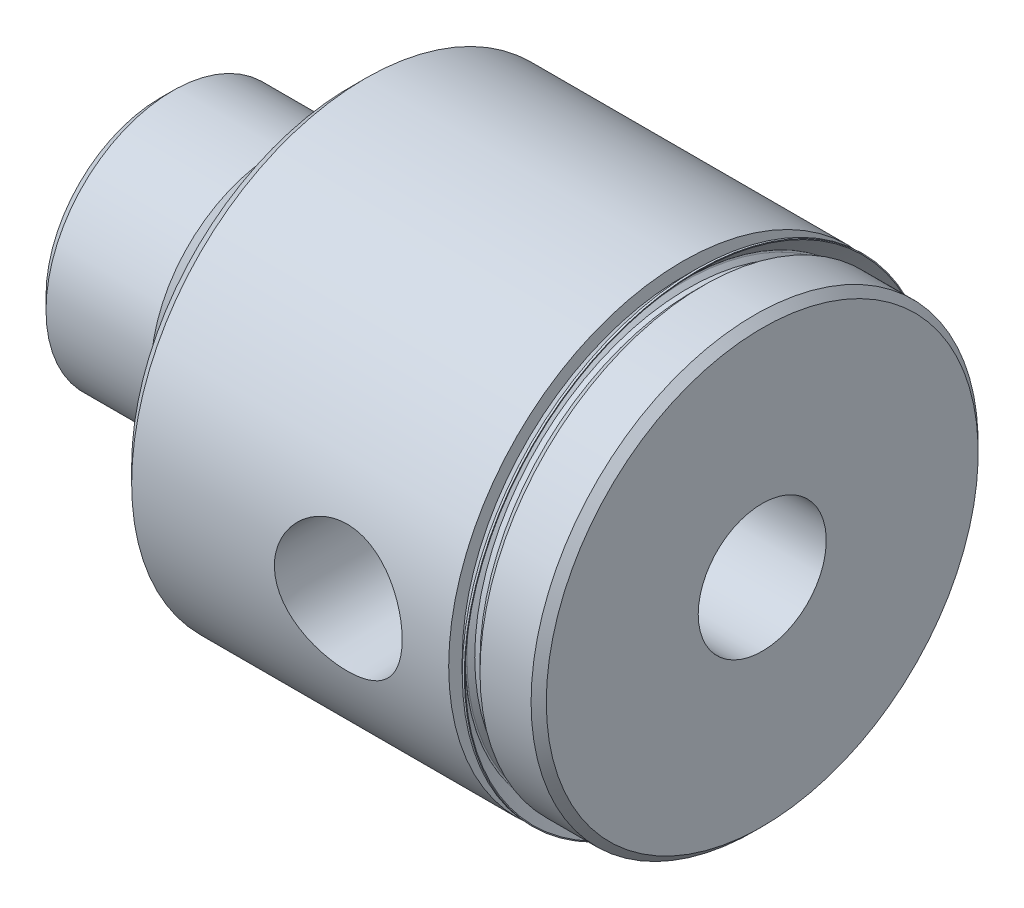
SolidWorks part; units mm, degrees
material "Cast Alloy Steel"
ref_plane "Front Plane" through (0, 0, 0) normal (0, 0, 1) x (1, 0, 0)
ref_plane "Top Plane" through (0, 0, 0) normal (0, 1, 0) x (1, 0, 0)
ref_plane "Right Plane" through (0, 0, 0) normal (1, 0, 0) x (0, 0, -1)
sketch "Sketch1" plane through (0, 0, 0) normal (0, 0, 1) x (1, 0, 0)
  line L0 (0, 0) -> (0, 11.4313)
  line L1 (0, 11.4313) -> (1.2687, 12.7)
  line L2 (1.2687, 12.7) -> (11.7862, 12.7)
  line L3 (11.7862, 12.7) -> (13.1292, 11.5708)
  line L4 (13.8811, 11.2966) -> (15.494, 11.2966)
  line L5 (16.6624, 12.4651) -> (16.6624, 13.0874)
  line L6 (16.6624, 13.0874) -> (19.05, 13.0874)
  line L7 (19.05, 13.0874) -> (19.05, 0)
  line L8 (19.05, 0) -> (0, 0)
  line L9 (19.05, 0) -> (0, 0) construction
  arc A0 (13.1292, 11.5708) -> (13.8811, 11.2966) centre (13.8811, 12.465) ccw
  arc A1 (15.494, 11.2966) -> (16.6624, 12.4651) centre (15.494, 12.4651) ccw
revolve "Revolve1" add sketch "Sketch1" angle 360 about L9 reverse direction yes
cosmetic thread "Cosmetic Thread1" parameters "D1"=13.0549, "D2"=22.8625
sketch "Sketch2" plane through (0, 0, 0) normal (0, 0, 1) x (1, 0, 0)
  line L0 (19.05, 0) -> (19.05, 21.9012)
  line L1 (19.05, 21.9012) -> (20.574, 23.4251)
  line L2 (20.574, 23.4251) -> (52.3367, 23.4251)
  line L3 (52.3367, 23.4251) -> (52.3367, 21.3423)
  line L4 (52.3367, 21.3423) -> (53.3908, 21.3423)
  line L5 (53.3908, 21.3423) -> (54.4449, 22.3965)
  line L6 (54.4449, 22.3965) -> (59.563, 22.3965)
  line L7 (59.563, 22.3965) -> (60.325, 21.6345)
  line L8 (60.325, 21.6345) -> (60.325, 0)
  line L9 (60.325, 0) -> (19.05, 0)
  line L10 (60.325, 0) -> (19.05, 0) construction
revolve "Revolve2" add sketch "Sketch2" angle 360 about L10 reverse direction yes
hole_wizard "Hole1" positions "Sketch4" profile "Sketch3" legacy
sketch "Sketch4" plane through (0, 0, 0) normal (-1, 0, 0) x (0, 0, 1)
  point P0 (0, 0)
sketch "Sketch3" plane through (0, 0, 0) normal (0, 1, 0) x (0, 0, 1)
  line L0 (0, 0) -> (0, 60.325)
  line L1 (0, 60.325) -> (6.4135, 60.325)
  line L2 (6.4135, 60.325) -> (6.4135, 0.762)
  line L3 (6.4135, 0.762) -> (7.1755, 0)
  line L4 (7.1755, 0) -> (0, 0)
  line L5 (0, -6.4453) -> (0, 115.525) construction
  line L6 (-6.4135, 0.762) -> (-7.1755, 0) construction
  dimension "Diameter" = 12.827
  dimension "Depth" = 60.325
  dimension "C-Sink Angle" = 90
  dimension "C-Sink Diameter" = 14.351
ref_plane "Plane1" through (0, 0, 0) normal (1, 0, 0) x (0, 0, -1)
ref_plane "Plane2" through (0, 0, 0) normal (1, 0, 0) x (0, 0, -1)
ref_plane "Plane3" through (0, 0, 0) normal (0, -0.7071, 0.7071) x (1, 0, 0)
ref_plane "Plane4" through (0, 0, 0) normal (1, 0, 0) x (0, 0, -1)
ref_plane "Plane5" through (52.3748, 0, 0) normal (1, 0, 0) x (0, 0, -1)
ref_plane "Plane6" through (19.05, 0, 0) normal (1, 0, 0) x (0, 0, -1)
ref_plane "Plane7" through (52.3748, 0, 0) normal (1, 0, 0) x (0, 0, -1)
sketch "Sketch5" plane through (0, 0, 0) normal (0, 1, 0) x (1, 0, 0)
  line L0 (41.275, 0) -> (44.45, 0)
  line L1 (44.45, 0) -> (44.45, -5.9261)
  line L2 (44.45, -5.9261) -> (47.2171, -8.6932)
  line L3 (47.2171, -8.6932) -> (47.677, -23.4251)
  line L4 (47.677, -23.4251) -> (41.275, -23.4251)
  line L5 (41.275, -23.4251) -> (41.275, 0)
  line L6 (41.275, -23.4251) -> (41.275, 0) construction
revolve "Cut-Revolve1" cut sketch "Sketch5" angle 360 about L6 reverse direction yes
cosmetic thread "Cosmetic Thread2" parameters "D1"=8.8392, "D2"=13.716
sketch "Sketch6" plane through (0, 0, 0) normal (0, 0, 1) x (1, 0, 0)
  line L0 (52.3367, 21.0883) -> (53.3908, 21.0883)
  line L1 (53.3908, 21.0883) -> (53.3908, 21.3423)
  line L2 (53.3908, 21.3423) -> (52.8638, 21.3423)
  line L3 (52.8638, 21.3423) -> (52.4717, 21.7344)
  line L4 (52.4717, 21.914) -> (53.8987, 23.341)
  line L5 (53.8987, 23.341) -> (53.8987, 23.4251)
  line L6 (53.8987, 23.4251) -> (53.6955, 23.4251)
  line L7 (53.6955, 23.4251) -> (52.3367, 22.0663)
  line L8 (52.3367, 22.0663) -> (52.3367, 21.0883)
  line L9 (53.3908, 0) -> (52.3367, 0) construction
  arc A0 (52.4717, 21.7344) -> (52.4717, 21.914) centre (52.5615, 21.8242) cw
revolve "Revolve3" add sketch "Sketch6" angle 360 about L9 reverse direction yes
ref_plane "Plane8" through (53.3908, 0, 0) normal (1, 0, 0) x (0, 0, -1)
ref_plane "Plane9" through (19.05, 0, 0) normal (1, 0, 0) x (0, 0, -1)
ref_plane "Plane10" through (16.6624, 0, 0) normal (1, 0, 0) x (0, 0, -1)
ref_plane "Plane11" through (0, 0, 0) normal (0, 1, 0) x (1, 0, 0)
ref_plane "Plane12" through (0, 0, 0) normal (0, 1, 0) x (1, 0, 0)
ref_plane "Plane13" through (19.05, 0, 0) normal (1, 0, 0) x (0, 0, -1)
ref_plane "Plane14" through (0, 0, 0) normal (0, 0, 1) x (1, 0, 0)
ref_plane "Plane15" through (0, 0, 0) normal (0, 1, 0) x (1, 0, 0)
ref_plane "Plane16" through (0, 0, 0) normal (0, 1, 0) x (1, 0, 0)
ref_plane "Plane17" through (0, 0, 0) normal (0, 1, 0) x (1, 0, 0)
ref_plane "Plane18" through (0, 0, 0) normal (1, 0, 0) x (0, 0, -1)
ref_plane "dp1 XY" through (0, 0, 0) normal (0, 0, 1) x (1, 0, 0)
ref_plane "dp1 XZ" through (0, 13.0874, 0) normal (0, -1, 0) x (-1, 0, 0)
ref_plane "dp1 YZ" through (19.05, 0, 0) normal (1, 0, 0) x (0, 0, -1)
ref_axis "dp1 X" through (-80.9, 13.0874, 0) along (1, 0, 0)
ref_axis "dp1 Y" through (19.05, -50, 0) along (0, 1, 0)
ref_axis "dp1 Z" through (19.05, 13.0874, 80.9) along (0, 0, -1)
sketch3d "dp1"
  point P0 (19.05, 13.0874, 0)
ref_plane "dp2 XY" through (0, 0, 0) normal (0, 0, 1) x (1, 0, 0)
ref_plane "dp2 XZ" through (0, -13.0874, 0) normal (0, -1, 0) x (-1, 0, 0)
ref_plane "dp2 YZ" through (19.05, 0, 0) normal (1, 0, 0) x (0, 0, -1)
ref_axis "dp2 X" through (-80.9, -13.0874, 0) along (1, 0, 0)
ref_axis "dp2 Y" through (19.05, -50, 0) along (0, 1, 0)
ref_axis "dp2 Z" through (19.05, -13.0874, 80.9) along (0, 0, -1)
sketch3d "dp2"
  point P0 (19.05, -13.0874, 0)
ref_plane "port XY" through (0, 0, 0) normal (0, 0, 1) x (1, 0, 0)
ref_plane "port XZ" through (0, 0, 0) normal (0, -1, 0) x (-1, 0, 0)
ref_plane "port YZ" through (41.275, 0, 0) normal (1, 0, 0) x (0, 0, -1)
ref_axis "port X" through (-80.9, 0, 0) along (1, 0, 0)
ref_axis "port Y" through (41.275, -50, 0) along (0, 1, 0)
ref_axis "port Z" through (41.275, 0, 80.9) along (0, 0, -1)
sketch3d "port"
  point P0 (41.275, 0, 0)
ref_plane "rod_guide XY" through (0, 0, 0) normal (1, 0, 0) x (0, 0, -1)
ref_plane "rod_guide XZ" through (0, 0, 0) normal (0, -1, 0) x (-1, 0, 0)
ref_plane "rod_guide YZ" through (0, 0, 0) normal (0, 0, -1) x (-1, 0, 0)
ref_axis "rod_guide X" through (0, 0, 80.9) along (0, 0, -1)
ref_axis "rod_guide Y" through (0, -50, 0) along (0, 1, 0)
ref_axis "rod_guide Z" through (80.9, 0, 0) along (-1, 0, 0)
sketch3d "rod_guide"
  point P0 (0, 0, 0)
ref_plane "s1 XY" through (0, 0, 0) normal (0, 0, 1) x (1, 0, 0)
ref_plane "s1 XZ" through (0, 0, 0) normal (0, -1, 0) x (-1, 0, 0)
ref_plane "s1 YZ" through (16.6624, 0, 0) normal (1, 0, 0) x (0, 0, -1)
ref_axis "s1 X" through (-80.9, 0, 0) along (1, 0, 0)
ref_axis "s1 Y" through (16.6624, -50, 0) along (0, 1, 0)
ref_axis "s1 Z" through (16.6624, 0, 80.9) along (0, 0, -1)
sketch3d "s1"
  point P0 (16.6624, 0, 0)
ref_plane "s2 XY" through (0, 0, 0) normal (0, 0, 1) x (1, 0, 0)
ref_plane "s2 XZ" through (0, 0, 0) normal (0, -1, 0) x (-1, 0, 0)
ref_plane "s2 YZ" through (19.05, 0, 0) normal (1, 0, 0) x (0, 0, -1)
ref_axis "s2 X" through (-80.9, 0, 0) along (1, 0, 0)
ref_axis "s2 Y" through (19.05, -50, 0) along (0, 1, 0)
ref_axis "s2 Z" through (19.05, 0, 80.9) along (0, 0, -1)
sketch3d "s2"
  point P0 (19.05, 0, 0)
ref_plane "t1 XY" through (19.05, 0, 0) normal (1, 0, 0) x (0, 0, -1)
ref_plane "t1 XZ" through (0, 0, 0) normal (0, -1, 0) x (-1, 0, 0)
ref_plane "t1 YZ" through (0, 0, 0) normal (0, 0, -1) x (-1, 0, 0)
ref_axis "t1 X" through (19.05, 0, 80.9) along (0, 0, -1)
ref_axis "t1 Y" through (19.05, -50, 0) along (0, 1, 0)
ref_axis "t1 Z" through (80.9, 0, 0) along (-1, 0, 0)
sketch3d "t1"
  point P0 (19.05, 0, 0)
ref_plane "t111 XY" through (19.05, 0, 0) normal (1, 0, 0) x (0, 0, -1)
ref_plane "t111 XZ" through (0, 0, 0) normal (0, -1, 0) x (-1, 0, 0)
ref_plane "t111 YZ" through (0, 0, 0) normal (0, 0, -1) x (-1, 0, 0)
ref_axis "t111 X" through (19.05, 0, 80.9) along (0, 0, -1)
ref_axis "t111 Y" through (19.05, -50, 0) along (0, 1, 0)
ref_axis "t111 Z" through (80.9, 0, 0) along (-1, 0, 0)
sketch3d "t111"
  point P0 (19.05, 0, 0)
ref_plane "to_foot_bracket XY" through (19.05, 0, 0) normal (1, 0, 0) x (0, 0, -1)
ref_plane "to_foot_bracket XZ" through (0, 0, 0) normal (0, -1, 0) x (-1, 0, 0)
ref_plane "to_foot_bracket YZ" through (0, 0, 0) normal (0, 0, -1) x (-1, 0, 0)
ref_axis "to_foot_bracket X" through (19.05, 0, 80.9) along (0, 0, -1)
ref_axis "to_foot_bracket Y" through (19.05, -50, 0) along (0, 1, 0)
ref_axis "to_foot_bracket Z" through (80.9, 0, 0) along (-1, 0, 0)
sketch3d "to_foot_bracket"
  point P0 (19.05, 0, 0)
ref_plane "to_nut XY" through (16.6624, 0, 0) normal (1, 0, 0) x (0, 0, -1)
ref_plane "to_nut XZ" through (0, 0, 0) normal (0, -1, 0) x (-1, 0, 0)
ref_plane "to_nut YZ" through (0, 0, 0) normal (0, 0, -1) x (-1, 0, 0)
ref_axis "to_nut X" through (16.6624, 0, 80.9) along (0, 0, -1)
ref_axis "to_nut Y" through (16.6624, -50, 0) along (0, 1, 0)
ref_axis "to_nut Z" through (80.9, 0, 0) along (-1, 0, 0)
sketch3d "to_nut"
  point P0 (16.6624, 0, 0)
ref_plane "to_rod XY" through (0, 0, 0) normal (1, 0, 0) x (0, 0, -1)
ref_plane "to_rod XZ" through (0, 0, 0) normal (0, -1, 0) x (-1, 0, 0)
ref_plane "to_rod YZ" through (0, 0, 0) normal (0, 0, -1) x (-1, 0, 0)
ref_axis "to_rod X" through (0, 0, 80.9) along (0, 0, -1)
ref_axis "to_rod Y" through (0, -50, 0) along (0, 1, 0)
ref_axis "to_rod Z" through (80.9, 0, 0) along (-1, 0, 0)
sketch3d "to_rod"
  point P0 (0, 0, 0)
ref_plane "to_screw XY" through (0, 0, 0) normal (0, 1, 0) x (1, 0, 0)
ref_plane "to_screw XZ" through (0, 0, 0) normal (0, 0, 1) x (1, 0, 0)
ref_plane "to_screw YZ" through (41.275, 0, 0) normal (1, 0, 0) x (0, 0, -1)
ref_axis "to_screw X" through (-80.9, 0, 0) along (1, 0, 0)
ref_axis "to_screw Y" through (41.275, 0, 50) along (0, 0, -1)
ref_axis "to_screw Z" through (41.275, 50, 0) along (0, -1, 0)
sketch3d "to_screw"
  point P0 (41.275, 0, 0)
ref_plane "to_trunnion_brackets XY" through (0, 0, 0) normal (0, 1, 0) x (1, 0, 0)
ref_plane "to_trunnion_brackets XZ" through (0, 0, 0) normal (0, 0, 1) x (1, 0, 0)
ref_plane "to_trunnion_brackets YZ" through (0, 0, 0) normal (1, 0, 0) x (0, 0, -1)
ref_axis "to_trunnion_brackets X" through (-80.9, 0, 0) along (1, 0, 0)
ref_axis "to_trunnion_brackets Y" through (0, 0, 50) along (0, 0, -1)
ref_axis "to_trunnion_brackets Z" through (0, 50, 0) along (0, -1, 0)
sketch3d "to_trunnion_brackets"
  point P0 (0, 0, 0)
ref_plane "to_trunnion_brackets1 XY" through (0, 0, 0) normal (0, 1, 0) x (1, 0, 0)
ref_plane "to_trunnion_brackets1 XZ" through (0, 0, 0) normal (0, 0, 1) x (1, 0, 0)
ref_plane "to_trunnion_brackets1 YZ" through (0, 0, 0) normal (1, 0, 0) x (0, 0, -1)
ref_axis "to_trunnion_brackets1 X" through (-80.9, 0, 0) along (1, 0, 0)
ref_axis "to_trunnion_brackets1 Y" through (0, 0, 50) along (0, 0, -1)
ref_axis "to_trunnion_brackets1 Z" through (0, 50, 0) along (0, -1, 0)
sketch3d "to_trunnion_brackets1"
  point P0 (0, 0, 0)
ref_plane "to_trunnion_brackets2 XY" through (0, 0, 0) normal (0, 1, 0) x (1, 0, 0)
ref_plane "to_trunnion_brackets2 XZ" through (0, 0, 0) normal (0, 0, 1) x (1, 0, 0)
ref_plane "to_trunnion_brackets2 YZ" through (0, 0, 0) normal (1, 0, 0) x (0, 0, -1)
ref_axis "to_trunnion_brackets2 X" through (-80.9, 0, 0) along (1, 0, 0)
ref_axis "to_trunnion_brackets2 Y" through (0, 0, 50) along (0, 0, -1)
ref_axis "to_trunnion_brackets2 Z" through (0, 50, 0) along (0, -1, 0)
sketch3d "to_trunnion_brackets2"
  point P0 (0, 0, 0)
ref_plane "to_tube XY" through (53.3908, 0, 0) normal (1, 0, 0) x (0, 0, -1)
ref_plane "to_tube XZ" through (0, 0, 0) normal (0, -1, 0) x (-1, 0, 0)
ref_plane "to_tube YZ" through (0, 0, 0) normal (0, 0, -1) x (-1, 0, 0)
ref_axis "to_tube X" through (53.3908, 0, 80.9) along (0, 0, -1)
ref_axis "to_tube Y" through (53.3908, -50, 0) along (0, 1, 0)
ref_axis "to_tube Z" through (80.9, 0, 0) along (-1, 0, 0)
sketch3d "to_tube"
  point P0 (53.3908, 0, 0)
